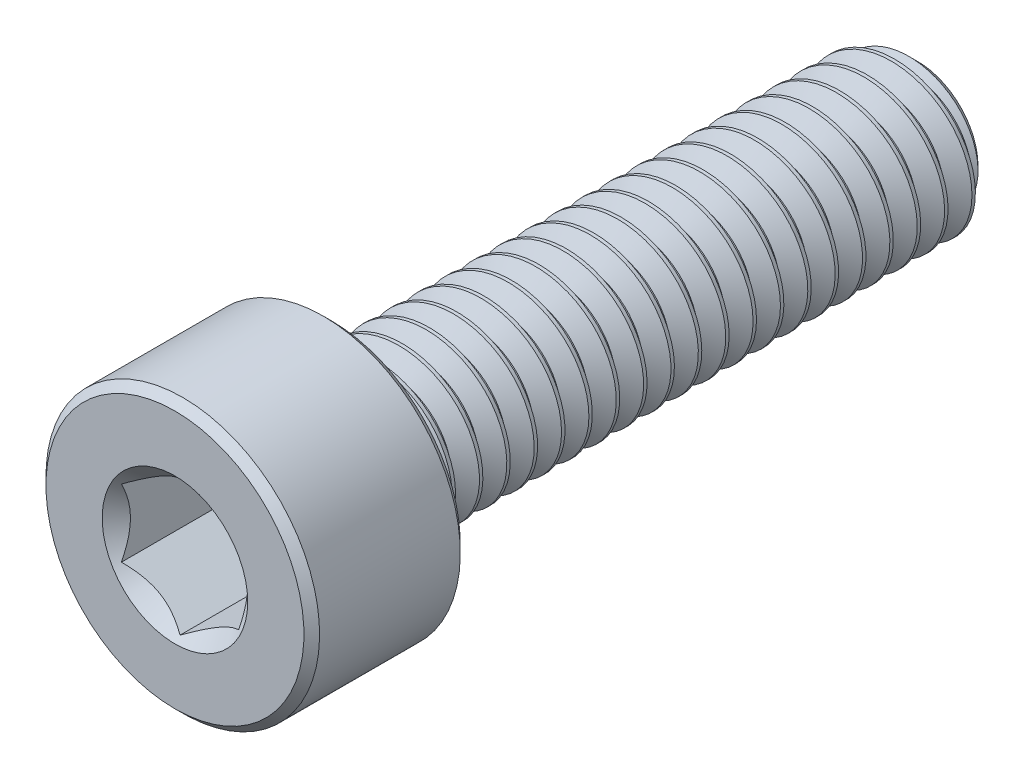
SolidWorks part; units mm, degrees
ref_plane "Front Plane" through (0, 0, 0) normal (0, 0, 1) x (1, 0, 0)
ref_plane "Top Plane" through (0, 0, 0) normal (0, 1, 0) x (1, 0, 0)
ref_plane "Right Plane" through (0, 0, 0) normal (1, 0, 0) x (0, 0, -1)
sketch "Sketch1" plane through (0, 0, 0) normal (1, 0, 0) x (0, 0, -1)
  line L0 (-9.5, 0) -> (9.5, 0) construction
  line L1 (9.5, 0) -> (9.5, 1.5453) construction
  line L2 (9.5, 1.5453) -> (9.0453, 2) construction
  line L3 (9.0453, 2) -> (8.975, 2) construction
  line L4 (8.975, 2) -> (-5.5, 2) construction
  line L5 (-5.5, 2) -> (-5.5, 3.5) construction
  line L6 (-5.5, 3.5) -> (-9.5, 3.5) construction
  line L7 (-9.5, 3.5) -> (-9.5, 0) construction
  line L8 (9.5, 1.5453) -> (9.5, 2) construction
  line L9 (9.4562, 2.0758) -> (9.8062, 1.4696) construction
  line L10 (9.8062, 1.4696) -> (10.1562, 2.0758) construction
  line L11 (10.1562, 2.0758) -> (9.4562, 2.0758) construction
  line L12 (9.8062, 2.0758) -> (9.8062, 2) construction
  line L13 (9.8062, 1.4696) -> (9.8062, 1.5453) construction
  line L14 (9.7625, 1.5453) -> (9.85, 1.5453) construction
  line L15 (9.5, 2) -> (10.1125, 2) construction
  line L16 (9.4781, 2.0379) -> (10.1344, 2.0379) construction
  line L17 (9.5, 0) -> (9.5, -2) construction
  line L18 (-5.7, 3.5) -> (-5.5, 3.3) construction
  line L19 (-9.3, 3.5) -> (-9.5, 3.3) construction
  line L20 (-5.5, 2) -> (-5.5, 0) construction
  line L21 (-5.5, 1) -> (-0.5, 1) construction
  line L22 (-0.5, 1) -> (4.5, 1) construction
  line L23 (4.5, 1) -> (9.5, 1) construction
  line L24 (-0.5, 1) -> (-0.5, 2) construction
  line L25 (-0.5, 2) -> (-0.5, 3.5) construction
  line L26 (4.5, 1) -> (4.5, 3.5) construction
  point P0 (-9.5, 1.5)
  point P3 (7.75, 2)
  point P4 (0, 0)
  point P18 (4.5, 2)
  point P22 (9.8062, 1.5453)
  point P24 (8.975, 2)
  point P25 (9.8062, 2)
  point P28 (9.8062, 2.0379)
  point P29 (7.75, -2)
  point P30 (-0.5, 2)
  point P31 (-7.5, 3.5)
  point P37 (-6.2, 3.5)
  point P38 (-9.2, 3.5)
  point P45 (-0.5, 1)
  point P46 (4.5, 1)
  dimension "D2" = 0.0875
  dimension "D7" = 0.2
  dimension "D8" = 0.2
  dimension "D9" = 0.2
  dimension "D10" = 0.1
  dimension "D11" = 0.5
  dimension "Drive Size" = 3
  dimension "Head Diameter" = 7
  dimension "Head Height" = 4
  dimension "Thread Pitch" = 0.7
  dimension "Thread Size" = 4
  dimension "Length" = 15
  dimension "D12" = 0.525
  dimension "D4" = 1.75
  dimension "D3" = 45
sketch "Sketch2" plane through (0, 0, 0) normal (1, 0, 0) x (0, 0, -1)
  line L0 (-9.5, 0) -> (-9.5, 3.3)
  line L1 (-9.3, 3.5) -> (-5.7, 3.5)
  line L2 (-5.5, 3.3) -> (-5.5, 2.2)
  line L4 (9.0453, 2) -> (9.5, 1.5453)
  line L5 (9.5, 1.5453) -> (9.5, 0)
  line L6 (-5.5, 3.5) -> (-9.5, 3.5) construction
  line L7 (9.5, 0) -> (-9.5, 0)
  line L8 (-9.3, 3.5) -> (-9.5, 3.3) construction
  line L10 (-9.3, 3.5) -> (-9.5, 3.3)
  line L14 (-5.7, 3.5) -> (-5.5, 3.3) construction
  line L16 (-5.7, 3.5) -> (-5.5, 3.3)
  line L17 (-5.5, 2) -> (-5.5, 3.5) construction
  line L19 (-5.3, 2) -> (9.0453, 2)
  line L20 (8.975, 2) -> (-5.5, 2) construction
  arc A1 (-5.5, 2.2) -> (-5.3, 2) centre (-5.3, 2.2) ccw
  dimension "D3" = 0.2
revolve "Revolve1" add sketch "Sketch2" angle 360 about L7
sketch "Sketch3" plane through (0, 0, 9.5) normal (0, 0, 1) x (1, 0, 0)
  line L1 (1.5, -0.866) -> (1.5, 0.866)
  line L2 (1.5, 0.866) -> (0, 1.7321)
  line L3 (0, 1.7321) -> (-1.5, 0.866)
  line L4 (-1.5, 0.866) -> (-1.5, -0.866)
  line L5 (-1.5, -0.866) -> (0, -1.7321)
  line L6 (0, -1.7321) -> (1.5, -0.866)
  circle A0 centre (0, 0) radius 1.5 construction
  circle A1 centre (0, 0) radius 3.5 construction
  circle A2 centre (0, 0) radius 3.5 construction
  circle A3 centre (0, 0) radius 1.7321 construction
  point P13 (0, 0)
  dimension "D1" = 3.4641
extrude "Cut-Extrude1" cut sketch "Sketch3" against normal offset from surface (3 mm away) 1 up to face at (0, 3.3, 5.5)
sketch "Sketch4" plane through (0, 0, 9.5) normal (0, 0, 1) x (1, 0, 0)
  circle A0 centre (0, 0) radius 1.862
  dimension "D1" = 3.7239
extrude "Cut-Extrude2" cut sketch "Sketch4" against normal up to vertex (2 mm away) draft 45 up to point (0, 3.5, 7.5)
sketch "Sketch11" plane through (0, 0, 0) normal (1, 0, 0) x (0, 0, -1)
  line L0 (-9.5, 0) -> (9.5, 0) construction
  line L1 (-9.5, 0) -> (9.5, 0) construction
  line L2 (-2.6875, 0) -> (-2.6875, 2) construction
  line L3 (8.975, 2) -> (-5.5, 2) construction
  line L4 (6.6875, 0) -> (6.6875, 2) construction
  line L6 (9.5, 1.5453) -> (9.5, 2) construction
  point P2 (-2.6875, 0)
  point P3 (6.6875, 0)
  dimension "D1" = 2.8125
  dimension "D2" = 2.8125
sketch "Sketch6" plane through (0, 0, -9.5) normal (0, 0, -1) x (-1, 0, 0)
  circle A0 centre (0, 0) radius 2
curve "Helix/Spiral1" pitch 0.7 height 15.7 turns 22.4286
sketch "Sketch10" plane through (0, 0, 0) normal (1, 0, 0) x (0, 0, -1)
  line L0 (-5.3, -3.5) -> (-5.3, 3.5)
  line L5 (-9.5, 0) -> (9.5, 0) construction
  line L6 (-5.3, 2) -> (-5.3, -2) construction
  point P3 (-5.3, 0)
split "Split1" trim tools "Sketch10" bodies to split 106 resulting bodies 114 115
sketch "Sketch7" plane through (0, 0, 0) normal (1, 0, 0) x (0, 0, -1)
  line L0 (9.4781, 2.0379) -> (10.1344, 2.0379)
  line L1 (10.1344, 2.0379) -> (9.85, 1.5453)
  line L2 (9.85, 1.5453) -> (9.7625, 1.5453)
  line L3 (9.7625, 1.5453) -> (9.4781, 2.0379)
sweep "Cut-Sweep1" cut profiles "Sketch7" path "Helix/Spiral1"
sketch "Sketch8" plane through (0, 0, 0) normal (1, 0, 0) x (0, 0, -1)
  line L0 (-5.5, 0) -> (-5.5, 2)
  line L1 (-5.3, -2) -> (-5.3, 2) construction
  line L2 (-5.5, 2) -> (-5.3, 2)
  line L4 (-5.3, 2) -> (-4.1453, 0)
  line L5 (-4.1453, 0) -> (-5.5, 0)
  line L6 (8.975, 2) -> (-5.5, 2) construction
  line L7 (-9.5, 0) -> (9.5, 0) construction
  dimension "D1" = 60
revolve "Revolve2" add sketch "Sketch8" angle 360 about L5
equation "\"D2@Sketch1\" = \"Thread Pitch@Sketch1\" / 8"
equation "\"D4@Helix/Spiral1\" = \"Thread Pitch@Sketch1\""
equation "\"D7@Sketch1\" = \"Head Height@Sketch1\" * .05"
equation "\"D8@Sketch1\"=\"D7@Sketch1\""
equation "\"D9@Sketch1\"=\"D7@Sketch1\""
equation "\"D10@Sketch1\"=\"D7@Sketch1\"/2"
equation "\"D11@Sketch1\"=\"D10@Sketch1\"*5"
equation "\"D4@Sketch1\"=\"Thread Pitch@Sketch1\"*2.5"
equation "\"D12@Sketch1\"=\"Thread Pitch@Sketch1\"*.75"
equation "\"D3@Helix/Spiral1\"=\"Length@Sketch1\"+\"Thread Pitch@Sketch1\""
equation "\"D3@Sketch2\"=\"Thread Size@Sketch1\"*0.05"
equation "\"D1@Sketch11\"=\"Length@Sketch1\"*0.1875"
equation "\"D2@Sketch11\"=\"D1@Sketch11\""
equation "\"D1@Sketch4\"=\"D1@Sketch3\"*1.075"
